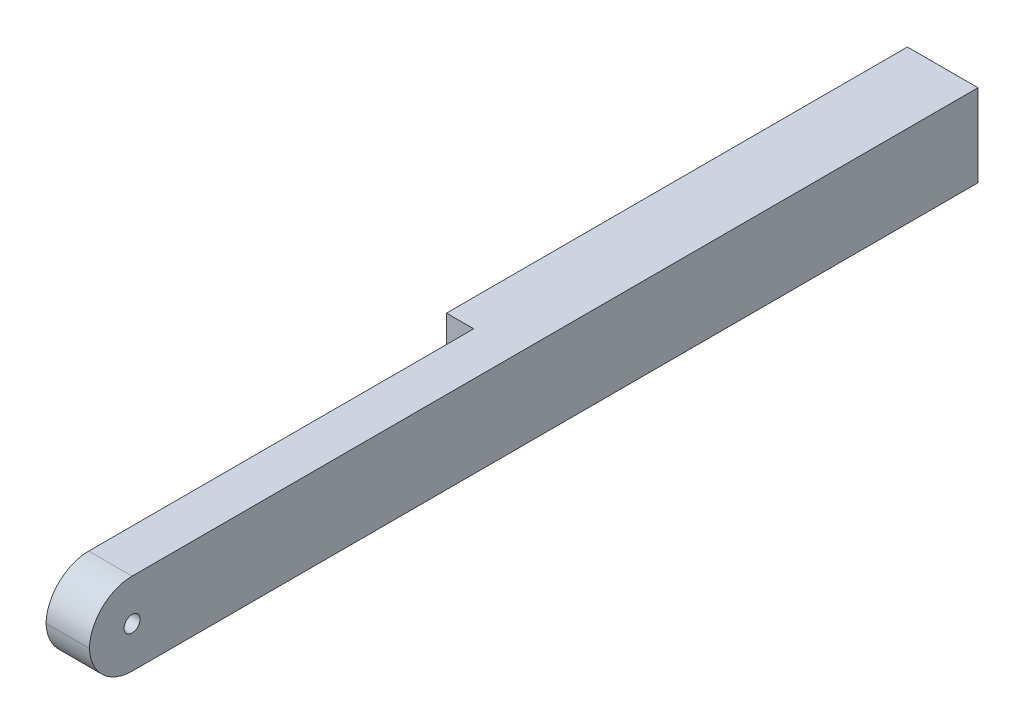
SolidWorks part; units mm, degrees
ref_plane "Ebene vorne" through (0, 0, 0) normal (0, 0, 1) x (1, 0, 0)
ref_plane "Ebene oben" through (0, 0, 0) normal (0, 1, 0) x (1, 0, 0)
ref_plane "Ebene rechts" through (0, 0, 0) normal (1, 0, 0) x (0, 0, -1)
sketch "Skizze1" plane through (0, 0, 0) normal (0, 0, 1) x (1, 0, 0)
  line L1 (-33, -38.5) -> (33, -38.5)
  line L2 (-33, -38.5) -> (-33, 38.5)
  line L3 (-33, 38.5) -> (33, 38.5)
  line L4 (33, -38.5) -> (33, 38.5)
  line L5 (-33, -38.5) -> (33, 38.5) construction
  line L6 (-33, 38.5) -> (33, -38.5) construction
  point P0 (0, 0)
  dimension "D1" = 77
  dimension "D2" = 66
extrude "Aufsatz-Linear austragen1" add sketch "Skizze1" along normal blind 831
sketch "Skizze2" plane through (0, 0, 0) normal (0, 0, -1) x (-1, 0, 0)
  line L0 (33, -20.5) -> (33, 8.5)
  line L1 (33, -20.5) -> (8, -20.5)
  line L2 (33, 8.5) -> (8, 8.5)
  line L3 (8, -20.5) -> (8, 8.5)
  line L4 (33, 38.5) -> (33, -38.5) construction
  line L5 (33, -38.5) -> (-33, -38.5) construction
  dimension "D1" = 18
  dimension "D2" = 25
  dimension "D3" = 29
extrude "Schnitt-Linear austragen1" cut sketch "Skizze2" against normal up to surface (831 mm away) up to face at (0, 0, 831)
sketch "Skizze3" plane through (-8, 0, 0) normal (-1, 0, 0) x (0, 0, 1)
  line L0 (18.367, -20.5) -> (10, -20.5)
  line L1 (0, -20.5) -> (3.0059, -12.2151)
  line L2 (3.0059, -12.2151) -> (5.361, -12.2151)
  line L3 (5.361, -12.2151) -> (8.367, -20.5)
  line L4 (831, -20.5) -> (0, -20.5) construction
  line L5 (8.367, -20.5) -> (0, -20.5)
  line L6 (10, -20.5) -> (13.0059, -12.2151)
  line L7 (13.0059, -12.2151) -> (15.361, -12.2151)
  line L8 (15.361, -12.2151) -> (18.367, -20.5)
  line L9 (28.367, -20.5) -> (20, -20.5)
  line L10 (20, -20.5) -> (23.0059, -12.2151)
  line L11 (23.0059, -12.2151) -> (25.361, -12.2151)
  line L12 (25.361, -12.2151) -> (28.367, -20.5)
  line L13 (38.367, -20.5) -> (30, -20.5)
  line L14 (30, -20.5) -> (33.0059, -12.2151)
  line L15 (33.0059, -12.2151) -> (35.361, -12.2151)
  line L16 (35.361, -12.2151) -> (38.367, -20.5)
  line L17 (48.367, -20.5) -> (40, -20.5)
  line L18 (40, -20.5) -> (43.0059, -12.2151)
  line L19 (43.0059, -12.2151) -> (45.361, -12.2151)
  line L20 (45.361, -12.2151) -> (48.367, -20.5)
  line L21 (58.367, -20.5) -> (50, -20.5)
  line L22 (50, -20.5) -> (53.0059, -12.2151)
  line L23 (53.0059, -12.2151) -> (55.361, -12.2151)
  line L24 (55.361, -12.2151) -> (58.367, -20.5)
  line L25 (68.367, -20.5) -> (60, -20.5)
  line L26 (60, -20.5) -> (63.0059, -12.2151)
  line L27 (63.0059, -12.2151) -> (65.361, -12.2151)
  line L28 (65.361, -12.2151) -> (68.367, -20.5)
  line L29 (78.367, -20.5) -> (70, -20.5)
  line L30 (70, -20.5) -> (73.0059, -12.2151)
  line L31 (73.0059, -12.2151) -> (75.361, -12.2151)
  line L32 (75.361, -12.2151) -> (78.367, -20.5)
  line L33 (88.367, -20.5) -> (80, -20.5)
  line L34 (80, -20.5) -> (83.0059, -12.2151)
  line L35 (83.0059, -12.2151) -> (85.361, -12.2151)
  line L36 (85.361, -12.2151) -> (88.367, -20.5)
  line L37 (98.367, -20.5) -> (90, -20.5)
  line L38 (90, -20.5) -> (93.0059, -12.2151)
  line L39 (93.0059, -12.2151) -> (95.361, -12.2151)
  line L40 (95.361, -12.2151) -> (98.367, -20.5)
  line L41 (108.367, -20.5) -> (100, -20.5)
  line L42 (100, -20.5) -> (103.0059, -12.2151)
  line L43 (103.0059, -12.2151) -> (105.361, -12.2151)
  line L44 (105.361, -12.2151) -> (108.367, -20.5)
  line L45 (118.367, -20.5) -> (110, -20.5)
  line L46 (110, -20.5) -> (113.0059, -12.2151)
  line L47 (113.0059, -12.2151) -> (115.361, -12.2151)
  line L48 (115.361, -12.2151) -> (118.367, -20.5)
  line L49 (128.367, -20.5) -> (120, -20.5)
  line L50 (120, -20.5) -> (123.0059, -12.2151)
  line L51 (123.0059, -12.2151) -> (125.361, -12.2151)
  line L52 (125.361, -12.2151) -> (128.367, -20.5)
  line L53 (138.367, -20.5) -> (130, -20.5)
  line L54 (130, -20.5) -> (133.0059, -12.2151)
  line L55 (133.0059, -12.2151) -> (135.361, -12.2151)
  line L56 (135.361, -12.2151) -> (138.367, -20.5)
  line L57 (148.367, -20.5) -> (140, -20.5)
  line L58 (140, -20.5) -> (143.0059, -12.2151)
  line L59 (143.0059, -12.2151) -> (145.361, -12.2151)
  line L60 (145.361, -12.2151) -> (148.367, -20.5)
  line L61 (158.367, -20.5) -> (150, -20.5)
  line L62 (150, -20.5) -> (153.0059, -12.2151)
  line L63 (153.0059, -12.2151) -> (155.361, -12.2151)
  line L64 (155.361, -12.2151) -> (158.367, -20.5)
  line L65 (168.367, -20.5) -> (160, -20.5)
  line L66 (160, -20.5) -> (163.0059, -12.2151)
  line L67 (163.0059, -12.2151) -> (165.361, -12.2151)
  line L68 (165.361, -12.2151) -> (168.367, -20.5)
  line L69 (178.367, -20.5) -> (170, -20.5)
  line L70 (170, -20.5) -> (173.0059, -12.2151)
  line L71 (173.0059, -12.2151) -> (175.361, -12.2151)
  line L72 (175.361, -12.2151) -> (178.367, -20.5)
  line L73 (188.367, -20.5) -> (180, -20.5)
  line L74 (180, -20.5) -> (183.0059, -12.2151)
  line L75 (183.0059, -12.2151) -> (185.361, -12.2151)
  line L76 (185.361, -12.2151) -> (188.367, -20.5)
  line L77 (198.367, -20.5) -> (190, -20.5)
  line L78 (190, -20.5) -> (193.0059, -12.2151)
  line L79 (193.0059, -12.2151) -> (195.361, -12.2151)
  line L80 (195.361, -12.2151) -> (198.367, -20.5)
  line L81 (208.367, -20.5) -> (200, -20.5)
  line L82 (200, -20.5) -> (203.0059, -12.2151)
  line L83 (203.0059, -12.2151) -> (205.361, -12.2151)
  line L84 (205.361, -12.2151) -> (208.367, -20.5)
  line L85 (218.367, -20.5) -> (210, -20.5)
  line L86 (210, -20.5) -> (213.0059, -12.2151)
  line L87 (213.0059, -12.2151) -> (215.361, -12.2151)
  line L88 (215.361, -12.2151) -> (218.367, -20.5)
  line L89 (228.367, -20.5) -> (220, -20.5)
  line L90 (220, -20.5) -> (223.0059, -12.2151)
  line L91 (223.0059, -12.2151) -> (225.361, -12.2151)
  line L92 (225.361, -12.2151) -> (228.367, -20.5)
  line L93 (238.367, -20.5) -> (230, -20.5)
  line L94 (230, -20.5) -> (233.0059, -12.2151)
  line L95 (233.0059, -12.2151) -> (235.361, -12.2151)
  line L96 (235.361, -12.2151) -> (238.367, -20.5)
  line L97 (248.367, -20.5) -> (240, -20.5)
  line L98 (240, -20.5) -> (243.0059, -12.2151)
  line L99 (243.0059, -12.2151) -> (245.361, -12.2151)
  line L100 (245.361, -12.2151) -> (248.367, -20.5)
  line L101 (258.367, -20.5) -> (250, -20.5)
  line L102 (250, -20.5) -> (253.0059, -12.2151)
  line L103 (253.0059, -12.2151) -> (255.361, -12.2151)
  line L104 (255.361, -12.2151) -> (258.367, -20.5)
  line L105 (268.367, -20.5) -> (260, -20.5)
  line L106 (260, -20.5) -> (263.0059, -12.2151)
  line L107 (263.0059, -12.2151) -> (265.361, -12.2151)
  line L108 (265.361, -12.2151) -> (268.367, -20.5)
  line L109 (278.367, -20.5) -> (270, -20.5)
  line L110 (270, -20.5) -> (273.0059, -12.2151)
  line L111 (273.0059, -12.2151) -> (275.361, -12.2151)
  line L112 (275.361, -12.2151) -> (278.367, -20.5)
  line L113 (288.367, -20.5) -> (280, -20.5)
  line L114 (280, -20.5) -> (283.0059, -12.2151)
  line L115 (283.0059, -12.2151) -> (285.361, -12.2151)
  line L116 (285.361, -12.2151) -> (288.367, -20.5)
  line L117 (298.367, -20.5) -> (290, -20.5)
  line L118 (290, -20.5) -> (293.0059, -12.2151)
  line L119 (293.0059, -12.2151) -> (295.361, -12.2151)
  line L120 (295.361, -12.2151) -> (298.367, -20.5)
  line L121 (308.367, -20.5) -> (300, -20.5)
  line L122 (300, -20.5) -> (303.0059, -12.2151)
  line L123 (303.0059, -12.2151) -> (305.361, -12.2151)
  line L124 (305.361, -12.2151) -> (308.367, -20.5)
  line L125 (318.367, -20.5) -> (310, -20.5)
  line L126 (310, -20.5) -> (313.0059, -12.2151)
  line L127 (313.0059, -12.2151) -> (315.361, -12.2151)
  line L128 (315.361, -12.2151) -> (318.367, -20.5)
  line L129 (328.367, -20.5) -> (320, -20.5)
  line L130 (320, -20.5) -> (323.0059, -12.2151)
  line L131 (323.0059, -12.2151) -> (325.361, -12.2151)
  line L132 (325.361, -12.2151) -> (328.367, -20.5)
  line L133 (338.367, -20.5) -> (330, -20.5)
  line L134 (330, -20.5) -> (333.0059, -12.2151)
  line L135 (333.0059, -12.2151) -> (335.361, -12.2151)
  line L136 (335.361, -12.2151) -> (338.367, -20.5)
  line L137 (348.367, -20.5) -> (340, -20.5)
  line L138 (340, -20.5) -> (343.0059, -12.2151)
  line L139 (343.0059, -12.2151) -> (345.361, -12.2151)
  line L140 (345.361, -12.2151) -> (348.367, -20.5)
  line L141 (358.367, -20.5) -> (350, -20.5)
  line L142 (350, -20.5) -> (353.0059, -12.2151)
  line L143 (353.0059, -12.2151) -> (355.361, -12.2151)
  line L144 (355.361, -12.2151) -> (358.367, -20.5)
  line L145 (368.367, -20.5) -> (360, -20.5)
  line L146 (360, -20.5) -> (363.0059, -12.2151)
  line L147 (363.0059, -12.2151) -> (365.361, -12.2151)
  line L148 (365.361, -12.2151) -> (368.367, -20.5)
  line L149 (378.367, -20.5) -> (370, -20.5)
  line L150 (370, -20.5) -> (373.0059, -12.2151)
  line L151 (373.0059, -12.2151) -> (375.361, -12.2151)
  line L152 (375.361, -12.2151) -> (378.367, -20.5)
  line L153 (388.367, -20.5) -> (380, -20.5)
  line L154 (380, -20.5) -> (383.0059, -12.2151)
  line L155 (383.0059, -12.2151) -> (385.361, -12.2151)
  line L156 (385.361, -12.2151) -> (388.367, -20.5)
  line L157 (398.367, -20.5) -> (390, -20.5)
  line L158 (390, -20.5) -> (393.0059, -12.2151)
  line L159 (393.0059, -12.2151) -> (395.361, -12.2151)
  line L160 (395.361, -12.2151) -> (398.367, -20.5)
  line L161 (408.367, -20.5) -> (400, -20.5)
  line L162 (400, -20.5) -> (403.0059, -12.2151)
  line L163 (403.0059, -12.2151) -> (405.361, -12.2151)
  line L164 (405.361, -12.2151) -> (408.367, -20.5)
  line L165 (418.367, -20.5) -> (410, -20.5)
  line L166 (410, -20.5) -> (413.0059, -12.2151)
  line L167 (413.0059, -12.2151) -> (415.361, -12.2151)
  line L168 (415.361, -12.2151) -> (418.367, -20.5)
  line L169 (428.367, -20.5) -> (420, -20.5)
  line L170 (420, -20.5) -> (423.0059, -12.2151)
  line L171 (423.0059, -12.2151) -> (425.361, -12.2151)
  line L172 (425.361, -12.2151) -> (428.367, -20.5)
  line L249 (8.367, -20.5) -> (18.367, -20.5) construction
  line L250 (438.367, -20.5) -> (430, -20.5) [skipped]
  line L251 (430, -20.5) -> (433.0059, -12.2151) [skipped]
  line L252 (433.0059, -12.2151) -> (435.361, -12.2151) [skipped]
  line L253 (435.361, -12.2151) -> (438.367, -20.5) [skipped]
  line L254 (448.367, -20.5) -> (440, -20.5) [skipped]
  line L255 (440, -20.5) -> (443.0059, -12.2151) [skipped]
  line L256 (443.0059, -12.2151) -> (445.361, -12.2151) [skipped]
  line L257 (445.361, -12.2151) -> (448.367, -20.5) [skipped]
  line L258 (458.367, -20.5) -> (450, -20.5) [skipped]
  line L259 (450, -20.5) -> (453.0059, -12.2151) [skipped]
  line L260 (453.0059, -12.2151) -> (455.361, -12.2151) [skipped]
  line L261 (455.361, -12.2151) -> (458.367, -20.5) [skipped]
  line L262 (468.367, -20.5) -> (460, -20.5) [skipped]
  line L263 (460, -20.5) -> (463.0059, -12.2151) [skipped]
  line L264 (463.0059, -12.2151) -> (465.361, -12.2151) [skipped]
  line L265 (465.361, -12.2151) -> (468.367, -20.5) [skipped]
  line L266 (478.367, -20.5) -> (470, -20.5) [skipped]
  line L267 (470, -20.5) -> (473.0059, -12.2151) [skipped]
  line L268 (473.0059, -12.2151) -> (475.361, -12.2151) [skipped]
  line L269 (475.361, -12.2151) -> (478.367, -20.5) [skipped]
  line L270 (488.367, -20.5) -> (480, -20.5) [skipped]
  line L271 (480, -20.5) -> (483.0059, -12.2151) [skipped]
  line L272 (483.0059, -12.2151) -> (485.361, -12.2151) [skipped]
  line L273 (485.361, -12.2151) -> (488.367, -20.5) [skipped]
  line L274 (498.367, -20.5) -> (490, -20.5) [skipped]
  line L275 (490, -20.5) -> (493.0059, -12.2151) [skipped]
  line L276 (493.0059, -12.2151) -> (495.361, -12.2151) [skipped]
  line L277 (495.361, -12.2151) -> (498.367, -20.5) [skipped]
  line L278 (508.367, -20.5) -> (500, -20.5) [skipped]
  line L279 (500, -20.5) -> (503.0059, -12.2151) [skipped]
  line L280 (503.0059, -12.2151) -> (505.361, -12.2151) [skipped]
  line L281 (505.361, -12.2151) -> (508.367, -20.5) [skipped]
  line L282 (518.367, -20.5) -> (510, -20.5) [skipped]
  line L283 (510, -20.5) -> (513.0059, -12.2151) [skipped]
  line L284 (513.0059, -12.2151) -> (515.361, -12.2151) [skipped]
  line L285 (515.361, -12.2151) -> (518.367, -20.5) [skipped]
  line L286 (528.367, -20.5) -> (520, -20.5) [skipped]
  line L287 (520, -20.5) -> (523.0059, -12.2151) [skipped]
  line L288 (523.0059, -12.2151) -> (525.361, -12.2151) [skipped]
  line L289 (525.361, -12.2151) -> (528.367, -20.5) [skipped]
  line L290 (538.367, -20.5) -> (530, -20.5) [skipped]
  line L291 (530, -20.5) -> (533.0059, -12.2151) [skipped]
  line L292 (533.0059, -12.2151) -> (535.361, -12.2151) [skipped]
  line L293 (535.361, -12.2151) -> (538.367, -20.5) [skipped]
  line L294 (548.367, -20.5) -> (540, -20.5) [skipped]
  line L295 (540, -20.5) -> (543.0059, -12.2151) [skipped]
  line L296 (543.0059, -12.2151) -> (545.361, -12.2151) [skipped]
  line L297 (545.361, -12.2151) -> (548.367, -20.5) [skipped]
  line L298 (558.367, -20.5) -> (550, -20.5) [skipped]
  line L299 (550, -20.5) -> (553.0059, -12.2151) [skipped]
  line L300 (553.0059, -12.2151) -> (555.361, -12.2151) [skipped]
  line L301 (555.361, -12.2151) -> (558.367, -20.5) [skipped]
  line L302 (568.367, -20.5) -> (560, -20.5) [skipped]
  line L303 (560, -20.5) -> (563.0059, -12.2151) [skipped]
  line L304 (563.0059, -12.2151) -> (565.361, -12.2151) [skipped]
  line L305 (565.361, -12.2151) -> (568.367, -20.5) [skipped]
  line L306 (578.367, -20.5) -> (570, -20.5) [skipped]
  line L307 (570, -20.5) -> (573.0059, -12.2151) [skipped]
  line L308 (573.0059, -12.2151) -> (575.361, -12.2151) [skipped]
  line L309 (575.361, -12.2151) -> (578.367, -20.5) [skipped]
  line L310 (588.367, -20.5) -> (580, -20.5) [skipped]
  line L311 (580, -20.5) -> (583.0059, -12.2151) [skipped]
  line L312 (583.0059, -12.2151) -> (585.361, -12.2151) [skipped]
  line L313 (585.361, -12.2151) -> (588.367, -20.5) [skipped]
  line L314 (598.367, -20.5) -> (590, -20.5) [skipped]
  line L315 (590, -20.5) -> (593.0059, -12.2151) [skipped]
  line L316 (593.0059, -12.2151) -> (595.361, -12.2151) [skipped]
  line L317 (595.361, -12.2151) -> (598.367, -20.5) [skipped]
  line L318 (608.367, -20.5) -> (600, -20.5) [skipped]
  line L319 (600, -20.5) -> (603.0059, -12.2151) [skipped]
  line L320 (603.0059, -12.2151) -> (605.361, -12.2151) [skipped]
  line L321 (605.361, -12.2151) -> (608.367, -20.5) [skipped]
  line L322 (618.367, -20.5) -> (610, -20.5) [skipped]
  line L323 (610, -20.5) -> (613.0059, -12.2151) [skipped]
  line L324 (613.0059, -12.2151) -> (615.361, -12.2151) [skipped]
  line L325 (615.361, -12.2151) -> (618.367, -20.5) [skipped]
  dimension "D1" = 10
  dimension "D2" = 62
extrude "Aufsatz-Linear austragen3" add sketch "Skizze3" along normal up to vertex (25 mm away) up to point (-33, -20.5, 0)
sketch "Skizze6" plane through (0, 0, 831) normal (0, 0, 1) x (1, 0, 0)
  line L0 (-33, 38.5) -> (-33, -38.5)
  line L1 (-33, 38.5) -> (-7.5521, 38.5)
  line L2 (-33, -38.5) -> (-7.5521, -38.5)
  line L3 (-7.5521, 38.5) -> (-7.5521, -38.5)
extrude "Schnitt-Linear austragen2" cut sketch "Skizze6" against normal blind 400
sketch "Skizze7" plane through (-7.5521, 0, 0) normal (-1, 0, 0) x (0, 0, 1)
  line L0 (831, -38.5) -> (831, 38.5) construction
  circle A0 centre (791, 0) radius 7.5
  point P4 (831, 0)
  dimension "D1" = 15
  dimension "D2" = 40
extrude "Schnitt-Linear austragen3" cut sketch "Skizze7" against normal up to surface (40.5521 mm away) up to face at (33, 0, 415.5)
fillet "Verrundung1" radius 40 2 edges at (12.7239, -38.5, 831) (12.7239, 38.5, 831)
move or copy body "Körper-Verschieben/Kopieren1" [suppressed] bodies to move or copy 108
